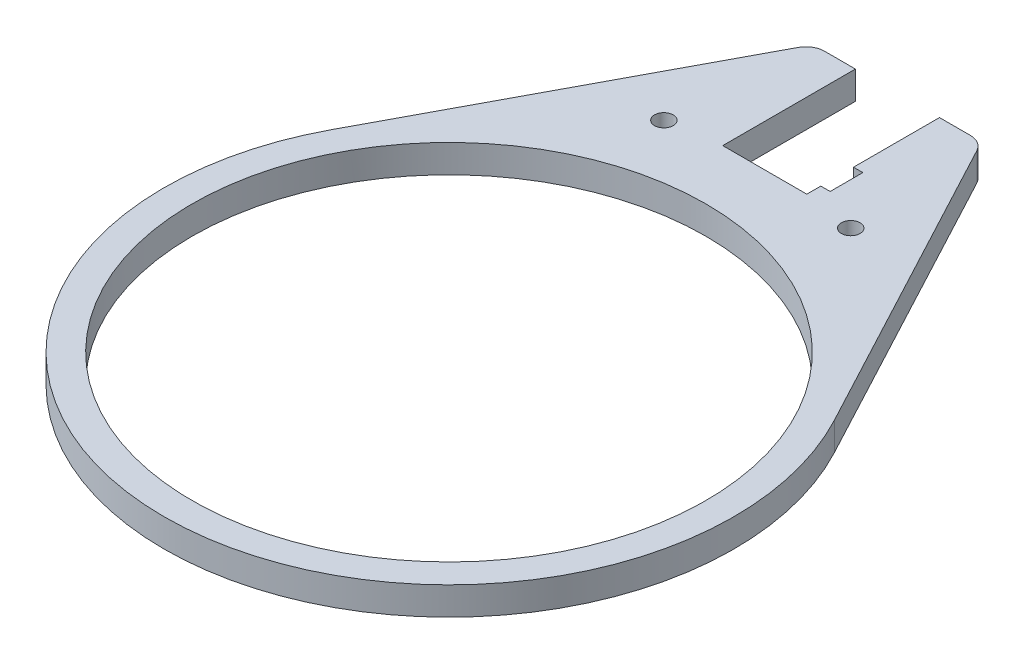
SolidWorks part; units mm, degrees
ref_plane "Front Plane" through (0, 0, 0) normal (0, 0, 1) x (1, 0, 0)
ref_plane "Top Plane" through (0, 0, 0) normal (0, 1, 0) x (1, 0, 0)
ref_plane "Right Plane" through (0, 0, 0) normal (1, 0, 0) x (0, 0, -1)
sketch "Sketch2" plane through (0, 0, 0) normal (0, 1, 0) x (1, 0, 0)
  line L0 (0, 0) -> (0, -50000) construction
  line L2 (-9.5, 67.8209) -> (9.5, 67.8209)
  line L3 (-12.5, 64.8209) -> (-12.5, 33.6749)
  line L5 (12.5, 64.8209) -> (12.5, 33.6749)
  line L6 (-12.5, 67.8209) -> (0, 48) construction
  line L7 (0, 48) -> (12.5, 67.8209) construction
  arc A0 (-16.9444, 25.3601) -> (16.9444, 25.3601) centre (0, 0) ccw
  arc A1 (12.5, 33.6749) -> (16.9444, 25.3601) centre (22.5, 33.6749) ccw
  arc A2 (-12.5, 33.6749) -> (-16.9444, 25.3601) centre (-22.5, 33.6749) cw
  arc A3 (9.5, 67.8209) -> (12.5, 64.8209) centre (9.5, 64.8209) cw
  arc A4 (-9.5, 67.8209) -> (-12.5, 64.8209) centre (-9.5, 64.8209) ccw
  point P5 (0, 48)
  point P10 (12.5, 27.8209)
  line B0 (-2.0588, 15.568) -> (-3.3995, 1.8156) construction
  line B1 (-3.3995, 1.8156) -> (-6.3417, 1.8292) construction
  line B2 (-6.3582, -1.7708) -> (-3.4161, -1.7843) construction
  line B3 (-3.4161, -1.7843) -> (-2.2018, -15.5484) construction
  line B4 (2.0588, -15.568) -> (3.3995, -1.8156) construction
  line B5 (3.3995, -1.8156) -> (6.3417, -1.8292) construction
  line B6 (6.3582, 1.7708) -> (3.4161, 1.7843) construction
  line B7 (3.4161, 1.7843) -> (2.2018, 15.5484) construction
  circle B8 centre (0.0233, 5.0782) radius 0.5 construction
  circle B9 centre (0.0325, 7.0717) radius 0.5 construction
  circle B10 centre (0.0426, 9.2662) radius 0.5 construction
  circle B11 centre (0.0514, 11.1888) radius 0.5 construction
  circle B12 centre (0.0608, 13.2337) radius 0.5 construction
  circle B13 centre (0.07, 15.2218) radius 0.5 construction
  circle B14 centre (-6.8538, 0.0315) radius 0.5 construction
  circle B15 centre (-4.9129, 0.0226) radius 0.5 construction
  circle B16 centre (-0.07, -15.2218) radius 0.5 construction
  circle B17 centre (-0.0608, -13.2337) radius 0.5 construction
  circle B18 centre (-0.0514, -11.1888) radius 0.5 construction
  circle B19 centre (-0.0426, -9.2662) radius 0.5 construction
  circle B20 centre (-0.0325, -7.0717) radius 0.5 construction
  circle B21 centre (-0.0233, -5.0782) radius 0.5 construction
  circle B22 centre (4.9129, -0.0226) radius 0.5 construction
  circle B23 centre (6.8538, -0.0315) radius 0.5 construction
  circle B24 centre (0, 0) radius 3.4 construction
  arc B25 (-6.3417, 1.8292) -> (-6.3582, -1.7708) centre (-6.3499, 0.0292) ccw construction
  arc B26 (-2.2018, -15.5484) -> (2.0588, -15.568) centre (-0.0706, -15.3604) ccw construction
  arc B27 (6.3417, -1.8292) -> (6.3582, 1.7708) centre (6.3499, -0.0292) ccw construction
  arc B28 (2.2018, 15.5484) -> (-2.0588, 15.568) centre (0.0706, 15.3604) ccw construction
  line B29 (3.5517, -15.7135) -> (4.7598, -3.3219)
  line B30 (4.7598, -3.3219) -> (6.3348, -3.3292)
  line B31 (6.3651, 3.2708) -> (4.7901, 3.278)
  line B32 (4.7901, 3.278) -> (3.696, 15.6802)
  line B33 (-3.5517, 15.7135) -> (-4.7598, 3.3219)
  line B34 (-4.7598, 3.3219) -> (-6.3348, 3.3292)
  line B35 (-6.3651, -3.2708) -> (-4.7901, -3.278)
  line B36 (-4.7901, -3.278) -> (-3.696, -15.6802)
  arc B37 (-3.696, -15.6802) -> (3.5517, -15.7135) centre (-0.0706, -15.3604) ccw
  arc B38 (6.3348, -3.3292) -> (6.3651, 3.2708) centre (6.3499, -0.0292) ccw
  arc B39 (3.696, 15.6802) -> (-3.5517, 15.7135) centre (0.0706, 15.3604) ccw
  arc B40 (-6.3348, 3.3292) -> (-6.3651, -3.2708) centre (-6.3499, 0.0292) ccw
  dimension "D1" = 61
  dimension "D5" = 10
  dimension "D6" = 3
  dimension "D2" = 25
  dimension "D3" = 48
  dimension "D4" = 40
sketch_block_instance "Block1-1"
sketch_block "Block1" parameters "D1"=70.3015
sketch_block_instance "Block1-1"
sketch_block "Block1" parameters "D1"=1.5
extrude "Boss-Extrude1" add sketch "Sketch2" along normal blind 1
sketch "Sketch3" plane through (0, 1, 0) normal (0, 1, 0) x (1, 0, 0)
  line L3 (-12.5, 64.8209) -> (-12.5, 33.6749)
  line L4 (9.5, 67.8209) -> (-9.5, 67.8209)
  line L5 (12.5, 33.6749) -> (12.5, 64.8209)
  line L6 (-12.5, 64.8209) -> (-12.5, 33.6749)
  line L7 (9.5, 67.8209) -> (-9.5, 67.8209)
  line L8 (12.5, 33.6749) -> (12.5, 64.8209)
  arc A5 (12.5, 33.6749) -> (16.9444, 25.3601) centre (22.5, 33.6749) ccw
  arc A6 (-16.9444, 25.3601) -> (16.9444, 25.3601) centre (0, 0) ccw
  arc A7 (-16.9444, 25.3601) -> (-12.5, 33.6749) centre (-22.5, 33.6749) ccw
  arc A8 (-9.5, 67.8209) -> (-12.5, 64.8209) centre (-9.5, 64.8209) ccw
  arc A9 (12.5, 64.8209) -> (9.5, 67.8209) centre (9.5, 64.8209) ccw
  arc A15 (12.5, 33.6749) -> (16.9444, 25.3601) centre (22.5, 33.6749) ccw
  arc A16 (-16.9444, 25.3601) -> (16.9444, 25.3601) centre (0, 0) ccw
  arc A17 (-16.9444, 25.3601) -> (-12.5, 33.6749) centre (-22.5, 33.6749) ccw
  arc A18 (-9.5, 67.8209) -> (-12.5, 64.8209) centre (-9.5, 64.8209) ccw
  arc A19 (12.5, 64.8209) -> (9.5, 67.8209) centre (9.5, 64.8209) ccw
  dimension "D1" = 0
extrude "Boss-Extrude2" add sketch "Sketch3" along normal blind 2
sketch "Sketch5" plane through (0, 1, 0) normal (0, -1, 0) x (1, 0, 0)
  circle A29 centre (0, 0) radius 2.25
  circle A34 centre (0.0227, 13.2339) radius 0.5
  circle A35 centre (-0.0227, -13.2339) radius 0.5
  line B0 (-2.1036, 15.562) -> (-3.4048, 1.8058)
  line B1 (-3.4048, 1.8058) -> (-6.3469, 1.8109)
  line B2 (-6.3531, -1.7891) -> (-3.4109, -1.7941)
  line B3 (-3.4109, -1.7941) -> (-2.157, -15.5547)
  line B4 (2.1036, -15.562) -> (3.4048, -1.8058)
  line B5 (3.4048, -1.8058) -> (6.3469, -1.8109)
  line B6 (6.3531, 1.7891) -> (3.4109, 1.7941)
  line B7 (3.4109, 1.7941) -> (2.157, 15.5547)
  circle B8 centre (0.0087, 5.0783) radius 0.5
  circle B9 centre (0.0121, 7.0718) radius 0.5
  circle B10 centre (0.0159, 9.2663) radius 0.5
  circle B11 centre (0.0192, 11.1889) radius 0.5
  circle B12 centre (0.0227, 13.2339) radius 0.5
  circle B13 centre (0.0261, 15.222) radius 0.5
  circle B14 centre (-6.8538, 0.0118) radius 0.5
  circle B15 centre (-4.9129, 0.0084) radius 0.5
  circle B16 centre (-0.0261, -15.222) radius 0.5
  circle B17 centre (-0.0227, -13.2339) radius 0.5
  circle B18 centre (-0.0192, -11.1889) radius 0.5
  circle B19 centre (-0.0159, -9.2663) radius 0.5
  circle B20 centre (-0.0121, -7.0718) radius 0.5
  circle B21 centre (-0.0087, -5.0783) radius 0.5
  circle B22 centre (4.9129, -0.0084) radius 0.5
  circle B23 centre (6.8538, -0.0118) radius 0.5
  circle B24 centre (0, 0) radius 3.4
  arc B25 (-6.3469, 1.8109) -> (-6.3531, -1.7891) centre (-6.35, 0.0109) ccw
  arc B26 (-2.157, -15.5547) -> (2.1036, -15.562) centre (-0.0264, -15.3605) ccw
  arc B27 (6.3469, -1.8109) -> (6.3531, 1.7891) centre (6.35, -0.0109) ccw
  arc B28 (2.157, 15.5547) -> (-2.1036, 15.562) centre (0.0264, 15.3605) ccw
  dimension "D1" = 4.5
sketch_block_instance "Block3-1"
sketch_block "Block3"
extrude "Cut-Extrude2" cut sketch "Sketch5" against normal through all contours A29 | A34 | A35 | B14 | B23 region at (0, 1, 0) region at (0.0227, 1, 13.2339) region at (-0.0227, 1, -13.2339)
sketch "Sketch6" plane through (0, 3, 0) normal (0, 1, 0) x (1, 0, 0)
  circle A0 centre (0, 0) radius 30.5
  arc A1 (-16.9444, 25.3601) -> (16.9444, 25.3601) centre (0, 0) ccw construction
extrude "Cut-Extrude3" cut sketch "Sketch6" against normal through all both and the other way through all flip side to cut
sketch "Sketch7" plane through (0, 0, 0) normal (0, -1, 0) x (1, 0, 0)
  line L0 (0, 0) -> (0, 50000) construction
  line L1 (-7.799, -48) -> (7.799, -48)
  line L2 (-26.9228, -14.3322) -> (-9.5644, -46.9398)
  line L3 (9.5644, -46.9398) -> (26.9228, -14.3322)
  line L4 (-26.9228, -14.3322) -> (0, -22.5493)
  line L5 (0, -22.5493) -> (26.9228, -14.3322)
  circle A0 centre (0, 0) radius 30.5 construction
  arc A1 (7.799, -48) -> (9.5644, -46.9398) centre (7.799, -46) ccw
  arc A2 (-7.799, -48) -> (-9.5644, -46.9398) centre (-7.799, -46) cw
  point P6 (0, -48)
  point P13 (9, -48)
  point P16 (-9, -48)
  dimension "D3" = 2
  dimension "D1" = 48
  dimension "D2" = 18
extrude "Boss-Extrude3" add sketch "Sketch7" against normal blind 3
sketch "Sketch8" plane through (0, 0, 0) normal (0, -1, 0) x (1, 0, 0)
  line L0 (0, -73) -> (0, 49927) construction
  line L1 (-7.799, -48) -> (7.799, -48) construction
  line L3 (-4.5, -62.2) -> (4.5, -62.2)
  line L4 (-4.5, -62.2) -> (-4.5, -33.8)
  line L5 (-4.5, -33.8) -> (4.5, -33.8)
  line L6 (4.5, -62.2) -> (4.5, -33.8)
  line L7 (-4.5, -62.2) -> (4.5, -33.8) construction
  line L8 (-4.5, -33.8) -> (4.5, -62.2) construction
  point P4 (0, -48)
  point P5 (0, -48)
  dimension "D1" = 9
  dimension "D2" = 14.2
extrude "Cut-Extrude4" cut sketch "Sketch8" against normal blind 3
sketch "Sketch10" plane through (0, 3, 0) normal (0, -1, 0) x (1, 0, 0)
  line L0 (4.5, -35.3) -> (5.5, -35.3)
  line L1 (5.5, -35.3) -> (5.5, -38.8)
  line L2 (5.5, -38.8) -> (3.606, -38.8)
  line L3 (3.606, -38.8) -> (3.606, -35.3)
  line L5 (3.606, -35.3) -> (4.5, -35.3)
  line L6 (4.5, -48) -> (4.5, -33.8) construction
  line L7 (0, -48) -> (0, -33.8) construction
  line L9 (4.5, -33.8) -> (-4.5, -33.8) construction
  line L16 (4.5, -48) -> (4.5, -33.8) construction
  line L17 (4.5, -48) -> (7.799, -48) construction
  line M36 (4.5, -48) -> (4.5, -33.8)
  dimension "D1" = 3.5
  dimension "D2" = 1
extrude "Cut-Extrude6" cut sketch "Sketch10" along normal blind 13 contours L3 L5 L2 M36 | L1 L2 L0 M36 region at (4.053, 3, -37.05) region at (5, 3, -37.05)
sketch "Sketch11" plane through (0, 0, 0) normal (0, -1, 0) x (1, 0, 0)
  line L1 (4.5, -33.8) -> (-4.5, -33.8)
  line L2 (4.5, -33.8) -> (4.5, -48)
  line L3 (4.5, -48) -> (-4.5, -48)
  line L4 (-4.5, -33.8) -> (-4.5, -48)
  circle A0 centre (0, 0) radius 30.5 construction
  arc A1 (26.9228, -14.3322) -> (-26.9228, -14.3322) centre (0, 0) ccw construction
  circle A2 centre (0, 0) radius 27.5
  dimension "D1" = 3
extrude "Cut-Extrude7" cut sketch "Sketch11" against normal through all both and the other way through all
sketch "Sketch12" plane through (0, 3, 0) normal (0, 1, 0) x (1, 0, 0)
  line L0 (0, 0) -> (0, -50000) construction
  line L1 (10, -0.563) -> (10, 49999.437) construction
  line L2 (-10, 0.4776) -> (-10, 50000.4776) construction
  line L3 (4.5, 33) -> (-49995.5, 33) construction
  circle A0 centre (-10, 33) radius 1
  circle A1 centre (10, 33) radius 1
  dimension "D3" = 2
  dimension "D1" = 10
  dimension "D2" = 10
  dimension "D4" = 33
extrude "Cut-Extrude8" cut sketch "Sketch12" against normal through all both and the other way through all
sketch "Sketch13" plane through (0, 3, 0) normal (0, 1, 0) x (1, 0, 0)
  line L0 (27.0111, 14.3792) -> (9.3286, 47.6024)
  line L1 (7.799, 48.1) -> (4.4, 48.1)
  line L2 (4.4, 48.1) -> (4.4, 38.7)
  line L3 (4.4, 38.7) -> (5.4, 38.7)
  line L4 (5.4, 38.7) -> (5.4, 35.4)
  line L5 (5.4, 35.4) -> (4.4, 35.4)
  line L6 (4.4, 35.4) -> (4.4, 33.9)
  line L7 (4.4, 33.9) -> (-4.4, 33.9)
  line L8 (-4.4, 33.9) -> (-4.4, 48.1)
  line L9 (-4.4, 48.1) -> (-7.799, 48.1)
  line L10 (-9.6527, 46.9868) -> (-27.0111, 14.3792)
  line L11 (7.799, 48) -> (4.5, 48)
  line L13 (7.799, 48) -> (4.5, 48)
  line L37 (4.5, 38.8) -> (5.5, 38.8)
  line L38 (4.5, 38.8) -> (5.5, 38.8)
  line L39 (5.5, 38.8) -> (5.5, 35.3)
  line L40 (5.5, 38.8) -> (5.5, 35.3)
  line L41 (4.5, 35.3) -> (4.5, 33.8)
  line L43 (4.5, 35.3) -> (4.5, 33.8)
  line L44 (7.799, 48) -> (4.5, 48) construction
  line L45 (4.5, 48) -> (4.5, 38.8) construction
  line L46 (4.5, 38.8) -> (5.5, 38.8) construction
  line L47 (5.5, 38.8) -> (5.5, 35.3) construction
  line L48 (5.5, 35.3) -> (4.5, 35.3) construction
  line L49 (4.5, 35.3) -> (4.5, 33.8) construction
  line L50 (4.5, 33.8) -> (-4.5, 33.8) construction
  line L51 (-4.5, 33.8) -> (-4.5, 48) construction
  line L52 (-4.5, 48) -> (-7.799, 48) construction
  line L53 (-9.5644, 46.9398) -> (-26.9228, 14.3322) construction
  line L54 (26.9228, 14.3322) -> (9.2513, 47.5349) construction
  line L56 (5.5, 35.3) -> (4.5, 35.3)
  line L58 (5.5, 35.3) -> (4.5, 35.3)
  line L60 (4.5, 48) -> (4.5, 38.8)
  line L61 (4.5, 48) -> (4.5, 38.8)
  line L68 (4.5, 33.8) -> (-4.5, 33.8)
  line L69 (4.5, 33.8) -> (-4.5, 33.8)
  line L70 (-4.5, 33.8) -> (-4.5, 48)
  line L71 (-4.5, 33.8) -> (-4.5, 48)
  line L72 (-4.5, 48) -> (-7.799, 48)
  line L73 (-4.5, 48) -> (-7.799, 48)
  line L74 (-9.5644, 46.9398) -> (-26.9228, 14.3322)
  line L75 (-9.5644, 46.9398) -> (-26.9228, 14.3322)
  line L76 (26.9228, 14.3322) -> (9.5644, 46.9398)
  line L77 (26.9228, 14.3322) -> (9.5644, 46.9398)
  circle A0 centre (0, 0) radius 27.4
  circle A1 centre (0, 0) radius 27.5
  circle A2 centre (0, 0) radius 27.5
  arc A3 (-7.799, 48) -> (-9.5644, 46.9398) centre (-7.799, 46) ccw
  arc A4 (-26.9228, 14.3322) -> (26.9228, 14.3322) centre (0, 0) ccw
  arc A7 (-26.9228, 14.3322) -> (26.9228, 14.3322) centre (0, 0) ccw
  circle A9 centre (10, 33) radius 1
  circle A11 centre (-10, 33) radius 1
  circle A13 centre (10, 33) radius 0.9
  circle A14 centre (-10, 33) radius 0.9
  arc A15 (9.3286, 47.6024) -> (7.799, 48.1) centre (7.799, 45.5) ccw
  arc A16 (-7.799, 48.1) -> (-9.6527, 46.9868) centre (-7.799, 46) ccw
  arc A17 (-27.0111, 14.3792) -> (27.0111, 14.3792) centre (0, 0) ccw
  circle A19 centre (10, 33) radius 1
  circle A20 centre (-10, 33) radius 1
  arc A21 (-7.799, 48) -> (-9.5644, 46.9398) centre (-7.799, 46) ccw construction
  arc A22 (9.2513, 47.5349) -> (7.799, 48) centre (7.799, 45.5) ccw construction
  arc A31 (-7.799, 48) -> (-9.5644, 46.9398) centre (-7.799, 46) ccw
  arc A32 (9.5644, 46.9398) -> (7.799, 48) centre (7.799, 46) ccw
  arc A33 (9.5644, 46.9398) -> (7.799, 48) centre (7.799, 46) ccw
  dimension "D1" = 0
  dimension "D2" = 0
  dimension "D3" = 0
  dimension "D4" = 0
  dimension "D5" = 0.1
  dimension "D6" = 0.1
extrude "Boss-Extrude4" [suppressed] add sketch "Sketch13" against normal up to surface (4 mm away)
